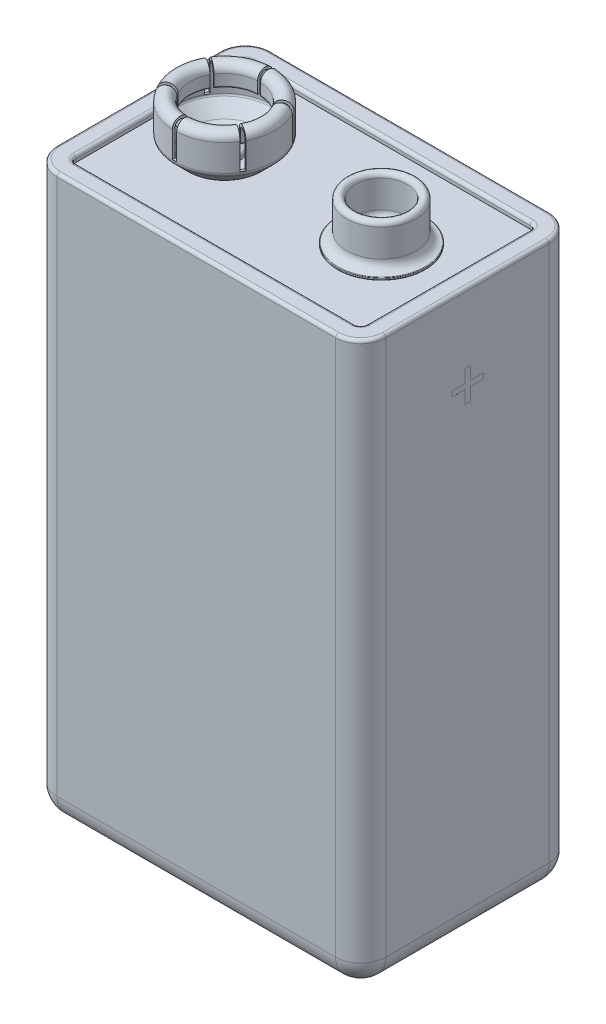
SolidWorks part; units mm, degrees
note: The reader was unsure of these and kept them because the rebuilt part matched: shared geometry of "Anschluss Pluspol_Skizze<3>".
material "1060 Legierung"
ref_plane "Ebene vorne" through (0, 0, 0) normal (0, 0, 1) x (1, 0, 0)
ref_plane "Ebene oben" through (0, 0, 0) normal (0, 1, 0) x (1, 0, 0)
ref_plane "Ebene rechts" through (0, 0, 0) normal (1, 0, 0) x (0, 0, -1)
sketch "Grundkörper_Skizze" plane through (0, 0, 0) normal (0, 1, 0) x (1, 0, 0)
  line L1 (13.1, -8.5) -> (-13.1, -8.5)
  line L2 (13.1, -8.5) -> (13.1, 8.5)
  line L3 (13.1, 8.5) -> (-13.1, 8.5)
  line L4 (-13.1, -8.5) -> (-13.1, 8.5)
  line L5 (13.1, -8.5) -> (-13.1, 8.5) construction
  line L6 (13.1, 8.5) -> (-13.1, -8.5) construction
  point P0 (0, 0)
  dimension "D1" = 17
  dimension "D2" = 26.2
extrude "Grundkörper_Aufsatz austragen" add sketch "Grundkörper_Skizze" along normal mid plane 45
fillet "Grundkörper_Verrundung" radius 2 8 edges at (0, -22.5, 8.5) (13.1, -22.5, 0) (0, -22.5, -8.5) (-13.1, -22.5, 0) (13.1, 0, -8.5) (-13.1, 0, -8.5) (13.1, 0, 8.5) (-13.1, 0, 8.5)
sketch "Vertiefung Anschlüsse_Skizze" plane through (0, 22.5, 0) normal (0, 1, 0) x (1, 0, 0)
  line L8 (11.6, -6.5) -> (11.6, 6.5)
  line L9 (11.1, 7) -> (-11.1, 7)
  line L10 (-11.6, 6.5) -> (-11.6, -6.5)
  line L11 (-11.1, -7) -> (11.1, -7)
  line L12 (11.6, -6.5) -> (11.6, 6.5)
  line L13 (11.1, 7) -> (-11.1, 7)
  line L14 (-11.6, 6.5) -> (-11.6, -6.5)
  line L15 (-11.1, -7) -> (11.1, -7)
  arc A8 (11.6, 6.5) -> (11.1, 7) centre (11.1, 6.5) ccw
  arc A9 (-11.1, 7) -> (-11.6, 6.5) centre (-11.1, 6.5) ccw
  arc A10 (-11.6, -6.5) -> (-11.1, -7) centre (-11.1, -6.5) ccw
  arc A11 (11.1, -7) -> (11.6, -6.5) centre (11.1, -6.5) ccw
  arc A12 (11.6, 6.5) -> (11.1, 7) centre (11.1, 6.5) ccw
  arc A13 (-11.1, 7) -> (-11.6, 6.5) centre (-11.1, 6.5) ccw
  arc A14 (-11.6, -6.5) -> (-11.1, -7) centre (-11.1, -6.5) ccw
  arc A15 (11.1, -7) -> (11.6, -6.5) centre (11.1, -6.5) ccw
  dimension "D1" = 1.5
extrude "Vertiefung Anschlüsse_Schnitt austragen" cut sketch "Vertiefung Anschlüsse_Skizze" against normal blind 0.5
fillet "Vertiefung Anschlüsse_Verrundung" radius 0.25 16 edges at (12.5142, 22.5, 7.9142) (0, 22.5, 8.5) (-12.5142, 22.5, 7.9142) (-13.1, 22.5, 0) (-12.5142, 22.5, -7.9142) (0, 22.5, -8.5) (12.5142, 22.5, -7.9142) (13.1, 22.5, 0) (11.6, 22.5, 0) (11.4536, 22.5, -6.8536) (0, 22.5, -7) (-11.4536, 22.5, -6.8536) (-11.6, 22.5, 0) (-11.4536, 22.5, 6.8536) (0, 22.5, 7) (11.4536, 22.5, 6.8536)
sketch "Anschlüsse_Skizze" plane through (0, 0, 0) normal (0, 0, 1) x (1, 0, 0)
  line L0 (9.75, 22.05) -> (9.75, 22.1516)
  line L1 (-11.1, 22) -> (11.1, 22) construction
  line L2 (9.7, 22) -> (6.25, 22)
  line L3 (7.5, 22.45) -> (7.8, 22.45)
  line L4 (8.3, 22.95) -> (8.3, 25.15)
  line L5 (-6.25, 0) -> (6.25, 0) construction
  line L6 (9, 22.95) -> (9, 25.15)
  line L7 (6.25, 22) -> (6.25, 22.3)
  line L8 (6.65, 22.7) -> (7.25, 22.7)
  line L9 (-7.5, 22.2) -> (-8.5, 22.2)
  line L10 (-6.25, 22) -> (-8.5, 22)
  line L12 (-9.2071, 22.2929) -> (-10.1339, 23.2197)
  line L15 (-9.9925, 23.3611) -> (-9.0657, 22.4343)
  line L18 (-10.25, 23.55) -> (-10.05, 23.55)
  line L19 (-10.05, 23.55) -> (-10.05, 23.5)
  line L20 (-10.25, 23.55) -> (-10.25, 23.5)
  line L21 (-6.65, 22.7) -> (-7.25, 22.7)
  line L22 (-6.25, 22) -> (-6.25, 22.3)
  line L23 (-7.5, 22.45) -> (-7.5, 22.2)
  line L24 (-10.25, 23.5) -> (-10.2592, 23.5071)
  arc A0 (9, 25.15) -> (8.3, 25.15) centre (8.65, 25.15) ccw
  arc A1 (9.7031, 22.2015) -> (9, 22.95) centre (9.75, 22.95) cw
  arc A2 (7.8, 22.45) -> (8.3, 22.95) centre (7.8, 22.95) ccw
  arc A3 (9.75, 22.05) -> (9.7, 22) centre (9.7, 22.05) cw
  arc A4 (9.75, 22.1516) -> (9.7031, 22.2015) centre (9.7, 22.1516) ccw
  arc A5 (6.25, 22.3) -> (6.4, 22.45) centre (6.25, 22.45) ccw
  arc A6 (6.4, 22.45) -> (6.65, 22.7) centre (6.65, 22.45) cw
  arc A7 (7.25, 22.7) -> (7.5, 22.45) centre (7.25, 22.45) cw
  arc A8 (-8.5, 22) -> (-9.2071, 22.2929) centre (-8.5, 23) cw
  arc A9 (-10.1339, 23.2197) -> (-10.25, 23.5) centre (-9.8536, 23.5) cw
  arc A12 (-9.9925, 23.3611) -> (-10.05, 23.5) centre (-9.8536, 23.5) cw
  arc A13 (-9.0657, 22.4343) -> (-8.5, 22.2) centre (-8.5, 23) ccw
  arc A14 (-7.25, 22.7) -> (-7.5, 22.45) centre (-7.25, 22.45) ccw
  arc A15 (-6.4, 22.45) -> (-6.65, 22.7) centre (-6.65, 22.45) ccw
  arc A16 (-6.25, 22.3) -> (-6.4, 22.45) centre (-6.25, 22.45) cw
  point P14 (8.65, 25.5)
  point P20 (9.75, 22)
  point P23 (9.75, 22.2)
  dimension "D1" = 3.5
  dimension "D3" = 3.5
  dimension "D4" = 0.7
  dimension "D6" = 0.5
  dimension "D7" = 0.05
  dimension "D9" = 1.25
  dimension "D12" = 0.15
  dimension "D10" = 0.25
  dimension "D13" = 0.15
  dimension "D15" = 0.25
  dimension "D21" = 1
  dimension "D2" = 12.5
  dimension "D5" = 0.2
  dimension "D8" = 2.75
  dimension "D11" = 0.3
  dimension "D14" = 1.25
  dimension "D16" = 0.2
  dimension "D17" = 0.3
  dimension "D18" = 4
  dimension "D24" = 135
  dimension "D25" = 1
  dimension "D26" = 1.5
  dimension "D27" = 0.05
revolve "Anschluss Pluspol_Rotation" add sketch "Anschlüsse_Skizze" angle 360 about L7
revolve "Anschluss Minuspol Basis_Rotation" add sketch "Anschluss Pluspol_Skizze<3>" angle 360 about L22
sketch "Anschluss Pluspol_Skizze<3>" plane through (0, 0, 0) normal (0, 0, 1) x (1, 0, 0) same geometry as "Anschlüsse_Skizze"
sketch "Anschluss Minuspol_Skizze" plane through (0, 0, 0) normal (0, 0, 1) x (1, 0, 0)
  line L0 (-10.25, 23.55) -> (-10.05, 23.55)
  line L1 (-10.25, 23.55) -> (-10.25, 25.625)
  line L2 (-9, 25.625) -> (-9, 24.75)
  line L3 (-9.2, 24.75) -> (-9.2, 25.625)
  line L4 (-10.05, 25.625) -> (-10.05, 23.55)
  line L5 (11.1, 22.25) -> (-11.1, 22.25) construction
  arc A0 (-10.25, 25.625) -> (-9, 25.625) centre (-9.625, 25.625) cw
  arc A1 (-9.2, 25.625) -> (-10.05, 25.625) centre (-9.625, 25.625) ccw
  arc A2 (-9, 24.75) -> (-9.2, 24.75) centre (-9.1, 24.75) cw
  point P10 (-9.625, 26.25)
  dimension "D1" = 1.25
  dimension "D2" = 0.2
  dimension "D3" = 1.5
  dimension "D4" = 4
revolve "Anschluss Minuspol_Rotation" add sketch "Anschluss Minuspol_Skizze" angle 55 mid plane
pattern_circular "Anschluss Minuspol_Kreismuster" count 6 over 360 about axis through (-6.25, 0, 0) along (0, 1, 0) of "Anschluss Minuspol_Rotation"
sketch "Beschriftung Pluspol_Skizze" plane through (13.1, 0, 0) normal (1, 0, 0) x (0, 0, -1)
  line L0 (-6.5, 17.5) -> (6.5, 17.5) construction
  line L1 (-6.5, 22.25) -> (-6.5, -20.5) construction
  line L2 (6.5, -20.5) -> (6.5, 22.25) construction
  line L3 (-6.5, 22.5) -> (6.5, 22.5) construction
  text T0 "<b>+</b>"
  dimension "D1" = 5
extrude "Beschriftung Pluspol_Schnitt austragen" cut sketch "Beschriftung Pluspol_Skizze" against normal blind 0.001
sketch "Beschriftung Minuspol_Skizze" plane through (-13.1, 0, 0) normal (-1, 0, 0) x (0, 0, 1)
  line L0 (-6.5, 17.5) -> (6.5, 17.5) construction
  line L1 (-6.5, 22.25) -> (-6.5, -20.5) construction
  line L2 (6.5, -20.5) -> (6.5, 22.25) construction
  line L3 (-6.5, 22.5) -> (6.5, 22.5) construction
  text T0 "−"
  dimension "D1" = 5
extrude "Beschriftung Minuspol_Schnitt austragen" cut sketch "Beschriftung Minuspol_Skizze" against normal blind 0.001
